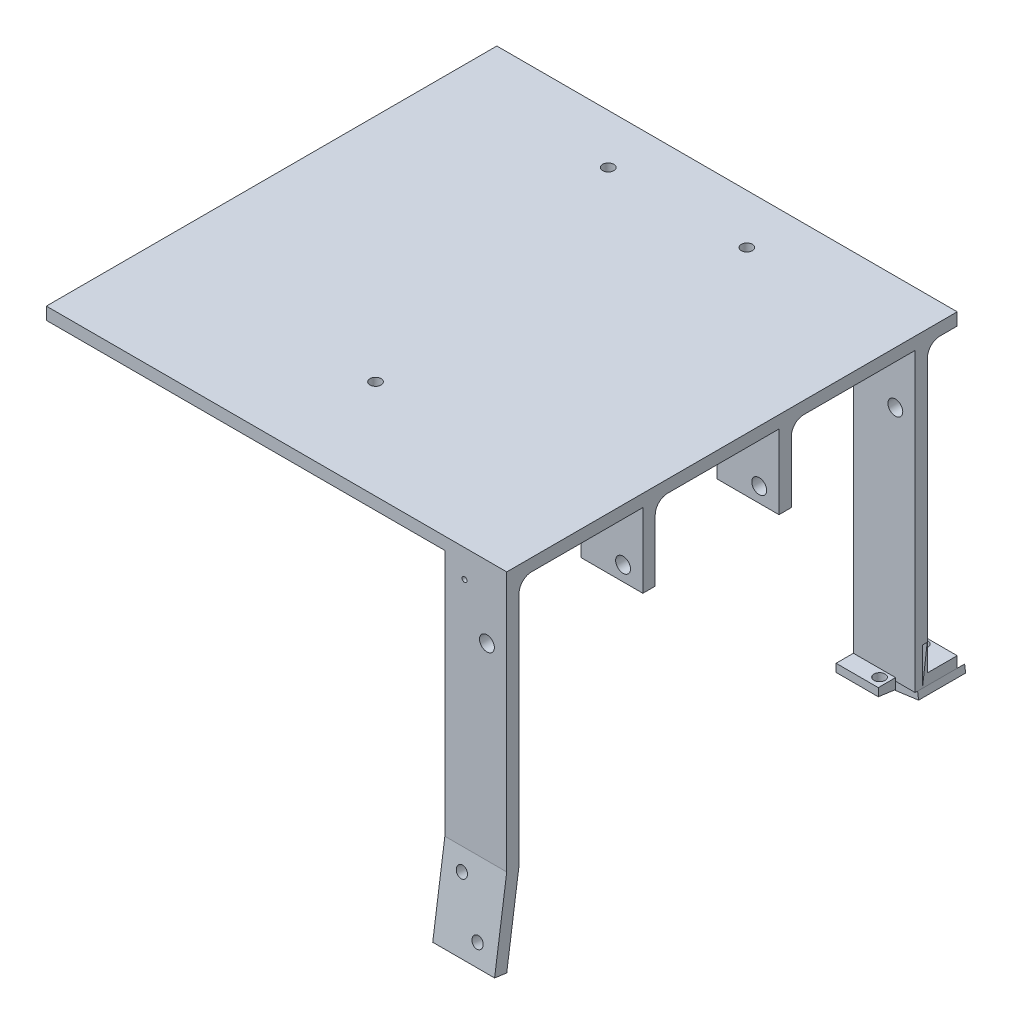
SolidWorks part; units mm, degrees
ref_plane "Front Plane" through (0, 0, 0) normal (0, 0, 1) x (1, 0, 0)
ref_plane "Top Plane" through (0, 0, 0) normal (0, 1, 0) x (1, 0, 0)
ref_plane "Right Plane" through (0, 0, 0) normal (1, 0, 0) x (0, 0, -1)
sketch "Sketch1" plane through (0, 0, 0) normal (0, 1, 0) x (1, 0, 0)
  line L0 (0, 0) -> (0, -300)
  line L1 (0, -300) -> (186, -300)
  line L2 (186, -300) -> (186, 0)
  line L3 (186, 0) -> (176, 0)
  line L4 (176, 0) -> (151, 0)
  line L5 (151, 0) -> (151, -56.1159)
  line L6 (151, -56.1159) -> (35, -56.1159)
  line L7 (35, -56.1159) -> (35, 0)
  line L8 (35, 0) -> (10, 0)
  line L9 (10, 0) -> (0, 0)
  line L10 (93, -300) -> (93, -56.1159) construction
  point P9 (93, -56.1159)
  dimension "D1" = 300
  dimension "D2" = 10
  dimension "D3" = 186
  dimension "D5" = 10
  dimension "D6" = 35
extrude "Boss-Extrude1" add sketch "Sketch1" along normal blind 5
sketch "Sketch2" plane through (0, 0, 0) normal (0, -1, 0) x (1, 0, 0)
  line L1 (50.5, 94) -> (55.5, 94)
  line L2 (50.5, 94) -> (50.5, 71.5)
  line L3 (50.5, 71.5) -> (55.5, 71.5)
  line L4 (55.5, 94) -> (55.5, 71.5)
  line L6 (135.5, 94) -> (130.5, 94)
  line L7 (135.5, 94) -> (135.5, 71.5)
  line L8 (135.5, 71.5) -> (130.5, 71.5)
  line L9 (130.5, 94) -> (130.5, 71.5)
  line L10 (0, 300) -> (186, 300) construction
  line L11 (186, 300) -> (186, 0) construction
  line L12 (0, 0) -> (0, 300) construction
  dimension "D1" = 5
  dimension "D2" = 22.5
  dimension "D3" = 5
  dimension "D4" = 206
  dimension "D5" = 22.5
  dimension "D6" = 50.5
  dimension "D7" = 50.5
extrude "Boss-Extrude2" add sketch "Sketch2" along normal blind 38
sketch "Sketch5" plane through (0, 0, 0) normal (0, -1, 0) x (1, 0, 0)
  line L0 (186, 300) -> (186, 0) construction
  line L1 (186, 295) -> (161, 295)
  line L2 (186, 295) -> (186, 300)
  line L3 (186, 300) -> (161, 300)
  line L4 (161, 295) -> (161, 300)
  line L5 (0, 300) -> (186, 300) construction
  line L6 (186, 240) -> (161, 240)
  line L7 (186, 240) -> (186, 245)
  line L8 (186, 245) -> (161, 245)
  line L9 (161, 240) -> (161, 245)
  line L10 (186, 185) -> (161, 185)
  line L11 (186, 185) -> (186, 190)
  line L12 (186, 190) -> (161, 190)
  line L13 (161, 185) -> (161, 190)
  line L14 (186, 130) -> (161, 130)
  line L15 (186, 130) -> (186, 135)
  line L16 (186, 135) -> (161, 135)
  line L17 (161, 130) -> (161, 135)
  dimension "D1" = 5
  dimension "D2" = 5
  dimension "D3" = 5
  dimension "D4" = 5
  dimension "D5" = 50
  dimension "D6" = 50
  dimension "D7" = 50
  dimension "D8" = 25
extrude "Boss-Extrude3" add sketch "Sketch5" along normal blind 30
fillet "Fillet3" radius 5 4 edges at (173.5, 0, 130) (173.5, 0, 185) (173.5, 0, 240) (173.5, 0, 295)
sketch "Sketch6" plane through (0, 0, 300) normal (0, 0, 1) x (1, 0, 0)
  line L0 (186, -30) -> (161, -30) construction
  line L1 (186, 5) -> (186, -30) construction
  circle A0 centre (178, -24) radius 3
  dimension "D1" = 6
  dimension "D2" = 6
  dimension "D3" = 8
extrude "Cut-Extrude4" cut sketch "Sketch6" against normal blind 172
sketch "Sketch7" plane through (0, 0, 0) normal (0, -1, 0) x (1, 0, 0)
  line L0 (0, 0) -> (0, 300) construction
  line L1 (0, 22.5) -> (5, 22.5)
  line L2 (0, 22.5) -> (0, 0)
  line L3 (0, 0) -> (5, 0)
  line L4 (5, 22.5) -> (5, 0)
  line L5 (186, 125) -> (186, 0) construction
  line L6 (186, 22.5) -> (181, 22.5)
  line L7 (186, 22.5) -> (186, 0)
  line L8 (186, 0) -> (181, 0)
  line L9 (181, 22.5) -> (181, 0)
  line L10 (186, 0) -> (151, 0) construction
  dimension "D1" = 5
  dimension "D2" = 5
  dimension "D3" = 22.5
  dimension "D4" = 22.5
extrude "Boss-Extrude4" add sketch "Sketch7" along normal blind 51.5
sketch "Sketch3" plane through (186, 0, 0) normal (1, 0, 0) x (0, 0, -1)
  line L4 (-71.5, 0) -> (-94, 0)
  line L5 (-71.5, -38) -> (-71.5, 0)
  line L6 (-94, -38) -> (-71.5, -38)
  line L7 (-94, 0) -> (-94, -38)
  line L9 (-71.5, -38) -> (-71.5, 0)
  line L10 (-94, -38) -> (-71.5, -38)
  line L11 (-94, 0) -> (-94, -38)
  line L13 (-71.5, 0) -> (-94, 0)
  circle A0 centre (-74, -32.9) radius 1.3 construction
  circle A1 centre (-91.5, -32.9) radius 1.3 construction
  circle A2 centre (-74, -32.9) radius 1.3
  circle A3 centre (-91.5, -32.9) radius 1.3
  circle A4 centre (-20, -46.4) radius 1.3 construction
  circle A5 centre (-2.5, -46.4) radius 1.3 construction
  circle A6 centre (-20, -46.4) radius 1.3
  circle A7 centre (-2.5, -46.4) radius 1.3
  dimension "D1" = 0
extrude "Cut-Extrude2" cut sketch "Sketch3" against normal through all contours A3 | A2 | A6 | A7
sketch "Sketch9" plane through (0, 0, 0) normal (0, -1, 0) x (1, 0, 0)
  line L0 (35, 0) -> (5, 0) construction
  line L1 (35, 0) -> (151, 0)
  line L2 (35, 0) -> (35, 63.7796)
  line L3 (35, 63.7796) -> (151, 63.7796)
  line L4 (151, 0) -> (151, 63.7796)
  line L5 (35, 56.1159) -> (35, 0) construction
  line L6 (151, 0) -> (151, 56.1159) construction
extrude "Cut-Extrude6" cut sketch "Sketch9" against normal blind 10
sketch "Sketch10" plane through (0, -30, 0) normal (0, -1, 0) x (1, 0, 0)
  line L1 (186, 295) -> (161, 295)
  line L2 (186, 295) -> (186, 300)
  line L3 (186, 300) -> (161, 300)
  line L4 (161, 295) -> (161, 300)
  line L5 (161, 130) -> (186, 130)
  line L6 (161, 130) -> (161, 135)
  line L7 (161, 135) -> (186, 135)
  line L8 (186, 130) -> (186, 135)
extrude "Boss-Extrude5" add sketch "Sketch10" along normal blind 70
sketch "Sketch11" plane through (186, 0, 0) normal (1, 0, 0) x (0, 0, -1)
  line L0 (-300, -100) -> (-304.9019, -134.6439)
  line L1 (-304.9019, -134.6439) -> (-300, -135.3374)
  line L2 (-300, -135.3374) -> (-295, -100)
  line L3 (-300, -100) -> (-295, -100)
extrude "Boss-Extrude6" add sketch "Sketch11" against normal blind 25
sketch "Sketch12" plane through (0, -100, 0) normal (0, -1, 0) x (1, 0, 0)
  line L1 (161, 130) -> (186, 130)
  line L2 (161, 130) -> (161, 135)
  line L3 (161, 135) -> (186, 135)
  line L4 (186, 130) -> (186, 135)
extrude "Boss-Extrude7" add sketch "Sketch12" along normal blind 19.72
sketch "Sketch13" plane through (0, 0, 130) normal (0, 0, -1) x (-1, 0, 0)
  line L0 (-186, -115.3141) -> (-186, -119.72)
  line L1 (-186, -119.72) -> (-186, -5) construction
  line L2 (-186, -119.72) -> (-161, -123.1352)
  line L3 (-161, -123.1352) -> (-161, -115.3141)
  line L4 (-161, -115.3141) -> (-186, -115.3141)
  line L5 (-161, -119.72) -> (-161, -5) construction
  line L8 (-88.5025, -135.5903) -> (-182.3051, -122.7762) construction
extrude "Boss-Extrude8" add sketch "Sketch13" along normal blind 15 and the other way blind 4
sketch "Sketch14" plane through (19.4625, -142.4702, 0) normal (0.1354, -0.9908, 0) x (0.9908, 0.1354, 0)
  line L0 (186.3576, 115) -> (168.0843, 132.0374)
  line L1 (168.0843, 115) -> (142.8521, 115) construction
  line L2 (168.0843, 115) -> (168.0843, 134) construction
  line L3 (168.0843, 132.0374) -> (198.0152, 130.431)
  line L4 (198.0152, 130.431) -> (197.5151, 111.3666)
  line L5 (197.5151, 111.3666) -> (186.3576, 109.6075)
  line L6 (186.3576, 109.6075) -> (186.3576, 115)
extrude "Cut-Extrude7" cut sketch "Sketch14" against normal blind 15
sketch "Sketch15" plane through (0, 39.652, 280.2402) normal (0, 0.1401, 0.9901) x (1, 0, 0)
  line L1 (161, -141.043) -> (161, -176.032) construction
  line L2 (186, -141.043) -> (161, -141.043) construction
  line L3 (186, -141.043) -> (186, -176.032) construction
  line L4 (161, -176.032) -> (186, -176.032) construction
  circle A0 centre (178, -168.032) radius 2.25
  circle A1 centre (169, -149.043) radius 2.25
  dimension "D1" = 4.5
  dimension "D2" = 4.5
  dimension "D3" = 8
  dimension "D4" = 8
  dimension "D5" = 8
  dimension "D6" = 8
extrude "Cut-Extrude8" cut sketch "Sketch15" against normal blind 20
sketch "Sketch16" plane through (0, 0, 0) normal (0, -1, 0) x (1, 0, 0)
  line L1 (166, 272) -> (172, 272)
  line L2 (166, 272) -> (166, 275)
  line L3 (166, 275) -> (172, 275)
  line L4 (172, 272) -> (172, 275)
  line L5 (143.4, 272) -> (137.4, 272)
  line L6 (143.4, 272) -> (143.4, 275)
  line L7 (143.4, 275) -> (137.4, 275)
  line L8 (137.4, 272) -> (137.4, 275)
  line L9 (166, 217) -> (172, 217)
  line L10 (166, 217) -> (166, 220)
  line L11 (166, 220) -> (172, 220)
  line L12 (172, 217) -> (172, 220)
  line L13 (166, 162) -> (172, 162)
  line L14 (166, 162) -> (166, 165)
  line L15 (166, 165) -> (172, 165)
  line L16 (172, 162) -> (172, 165)
  line L17 (137.4, 217) -> (143.4, 217)
  line L18 (137.4, 217) -> (137.4, 220)
  line L19 (137.4, 220) -> (143.4, 220)
  line L20 (143.4, 217) -> (143.4, 220)
  line L21 (137.4, 162) -> (143.4, 162)
  line L22 (137.4, 162) -> (137.4, 165)
  line L23 (137.4, 165) -> (143.4, 165)
  line L24 (143.4, 162) -> (143.4, 165)
  line L25 (186, 180) -> (186, 135) construction
  line L28 (161, 295) -> (186, 295) construction
  line L29 (161, 240) -> (186, 240) construction
  line L30 (161, 185) -> (186, 185) construction
  dimension "D1" = 3
  dimension "D2" = 3
  dimension "D3" = 3
  dimension "D4" = 3
  dimension "D5" = 3
  dimension "D6" = 3
  dimension "D7" = 20
  dimension "D8" = 22.6
  dimension "D9" = 6
  dimension "D10" = 6
  dimension "D11" = 23
  dimension "D12" = 23
  dimension "D13" = 23
extrude "Boss-Extrude9" add sketch "Sketch16" along normal blind 12.4
sketch "Sketch17" plane through (0, 0, 162) normal (0, 0, -1) x (-1, 0, 0)
  arc A0 (-169.75, -6.8) -> (-169.75, -5.6) centre (-168.95, -6.2) ccw construction
  arc A1 (-169.75, -6.8) -> (-169.75, -5.6) centre (-168.95, -6.2) ccw
  circle A2 centre (-168.95, -6.2) radius 1
  circle A3 centre (-140.45, -6.2) radius 1
extrude "Cut-Extrude9" cut sketch "Sketch17" against normal through all contours A1 A2 | A3 region at (168.95, -6.2, 162)
sketch "Sketch27" plane through (19.4625, -142.4702, 0) normal (0.1354, -0.9908, 0) x (0.9908, 0.1354, 0)
  line L1 (142.8521, 115) -> (168.0843, 115)
  line L2 (142.8521, 115) -> (142.8521, 134)
  line L3 (142.8521, 134) -> (168.0843, 134)
  line L4 (168.0843, 115) -> (168.0843, 134)
extrude "Boss-Extrude11" add sketch "Sketch27" along normal blind 3
fillet "Fillet4" radius 5 6 edges at (140.4, 0, 275) (169, 0, 275) (140.4, 0, 220) (169, 0, 220) (140.4, 0, 165) (169, 0, 165)
sketch "Sketch18" plane through (0, -115.3141, 0) normal (0, 1, 0) x (1, 0, 0)
  circle A0 centre (174.8857, -120.9947) radius 2.25
  dimension "D1" = 4.5
extrude "Cut-Extrude10" cut sketch "Sketch18" against normal through all
sketch "Sketch19" plane through (0, 0, 0) normal (0, -1, 0) x (1, 0, 0)
  line L0 (42.3, 80.75) -> (39.8, 80.75) construction
  line L1 (39.8, 84.75) -> (39.8, 80.75) construction
  line L2 (42.3, 84.75) -> (42.3, 80.75) construction
  line L3 (39.8, 84.75) -> (42.3, 84.75) construction
  line L4 (42.3, 80.75) -> (39.8, 80.75) construction
  line L5 (39.8, 84.75) -> (39.8, 80.75) construction
  line L6 (42.3, 84.75) -> (42.3, 80.75) construction
  line L7 (39.8, 84.75) -> (42.3, 84.75) construction
  line L8 (143.7, 80.75) -> (143.7, 84.75) construction
  line L9 (143.7, 84.75) -> (146.2, 84.75) construction
  line L10 (146.2, 80.75) -> (146.2, 84.75) construction
  line L11 (146.2, 80.75) -> (143.7, 80.75) construction
  line L12 (143.7, 80.75) -> (143.7, 84.75) construction
  line L13 (143.7, 84.75) -> (146.2, 84.75) construction
  line L14 (146.2, 80.75) -> (146.2, 84.75) construction
  line L15 (146.2, 80.75) -> (143.7, 80.75) construction
  line L16 (43.3, 79.75) -> (38.8, 79.75)
  line L17 (38.8, 85.75) -> (38.8, 79.75)
  line L18 (38.8, 85.75) -> (43.3, 85.75)
  line L19 (43.3, 85.75) -> (43.3, 79.75)
  line L20 (142.7, 79.75) -> (142.7, 85.75)
  line L21 (142.7, 85.75) -> (147.2, 85.75)
  line L22 (147.2, 79.75) -> (147.2, 85.75)
  line L23 (147.2, 79.75) -> (142.7, 79.75)
  line L31 (151, 0) -> (181, 0)
  line L32 (181, 0) -> (181, 22.5)
  line L34 (186, 22.5) -> (186, 125)
  line L35 (186, 125) -> (161, 125)
  line L36 (161, 125) -> (161, 135)
  line L37 (161, 135) -> (186, 135)
  line L38 (186, 135) -> (186, 180)
  line L39 (186, 180) -> (161, 180)
  line L40 (161, 180) -> (161, 190)
  line L41 (161, 190) -> (186, 190)
  line L42 (186, 190) -> (186, 235)
  line L43 (186, 235) -> (161, 235)
  line L44 (161, 235) -> (161, 245)
  line L45 (161, 245) -> (186, 245)
  line L46 (186, 245) -> (186, 290)
  line L47 (186, 290) -> (161, 290)
  line L48 (161, 290) -> (161, 300)
  line L49 (161, 300) -> (0, 300)
  line L50 (0, 300) -> (0, 22.5)
  line L51 (0, 22.5) -> (5, 22.5)
  line L52 (5, 22.5) -> (5, 0)
  line L53 (5, 0) -> (35, 0)
  line L56 (151, 63.7796) -> (151, 0)
  line L57 (151, 63.7796) -> (151, 0)
  line L58 (35, 0) -> (35, 63.7796)
  line L61 (151, 0) -> (181, 0)
  line L64 (186, 22.5) -> (186, 125)
  line L65 (186, 125) -> (161, 125)
  line L66 (161, 125) -> (161, 135)
  line L67 (161, 135) -> (186, 135)
  line L68 (186, 135) -> (186, 180)
  line L69 (186, 180) -> (161, 180)
  line L70 (161, 180) -> (161, 190)
  line L71 (161, 190) -> (186, 190)
  line L72 (186, 190) -> (186, 235)
  line L73 (186, 235) -> (161, 235)
  line L74 (161, 235) -> (161, 245)
  line L75 (161, 245) -> (186, 245)
  line L76 (186, 245) -> (186, 290)
  line L77 (186, 290) -> (161, 290)
  line L78 (161, 290) -> (161, 300)
  line L79 (161, 300) -> (0, 300)
  line L80 (0, 300) -> (0, 22.5)
  line L81 (0, 22.5) -> (5, 22.5)
  line L82 (5, 22.5) -> (5, 0)
  line L83 (5, 0) -> (35, 0)
  line L106 (35, 0) -> (35, 63.7796)
  line L107 (35, 63.7796) -> (151, 63.7796)
  line L108 (35, 63.7796) -> (151, 63.7796)
  line L116 (181, 22.5) -> (186, 22.5)
  line L122 (181, 22.5) -> (186, 22.5)
  line L124 (181, 0) -> (181, 22.5)
  dimension "D1" = 0
  dimension "D2" = 1
  dimension "D3" = 1
extrude "Cut-Extrude12" cut sketch "Sketch19" against normal through all contours L23 L22 L21 L20 | L19 L18 L17 L16 region at (41.05, 0, 82.75) region at (144.95, 0, 82.75)
fillet "Fillet6" radius 10 2 edges at (151, 2.5, 63.7796) (35, 2.5, 63.7796)
sketch "Sketch21" plane through (0, 0, 0) normal (0, -1, 0) x (1, 0, 0)
  line L0 (0, 22.5) -> (0, 300) construction
  line L1 (0, 48) -> (27, 48)
  line L2 (0, 48) -> (0, 118)
  line L3 (0, 118) -> (27, 118)
  line L4 (27, 48) -> (27, 118)
  line L5 (186, 125) -> (186, 22.5) construction
  line L6 (186, 48) -> (159, 48)
  line L7 (186, 48) -> (186, 118)
  line L8 (186, 118) -> (159, 118)
  line L9 (159, 48) -> (159, 118)
  line L10 (0, 300) -> (161, 300) construction
  dimension "D1" = 70
  dimension "D2" = 182
  dimension "D3" = 70
  dimension "D4" = 182
  dimension "D5" = 27
  dimension "D6" = 27
extrude "Cut-Extrude14" cut sketch "Sketch21" against normal through all
fillet "Fillet7" radius 10 4 edges at (27, 2.5, 118) (27, 2.5, 48) (159, 2.5, 48) (159, 2.5, 118)
fillet "Fillet8" radius 2.5 2 edges at (55.5, 0, 82.75) (130.5, 0, 82.75)
sketch "Sketch22" plane through (0, 0, 0) normal (0, -1, 0) x (1, 0, 0)
  line L34 (17, 48) -> (0, 48)
  line L35 (0, 48) -> (0, 22.5)
  line L36 (0, 22.5) -> (5, 22.5)
  line L37 (5, 22.5) -> (5, 0)
  line L38 (5, 0) -> (35, 0)
  line L39 (35, 0) -> (35, 53.7796)
  line L40 (45, 63.7796) -> (141, 63.7796)
  line L41 (151, 53.7796) -> (151, 0)
  line L42 (151, 0) -> (181, 0)
  line L43 (181, 0) -> (181, 22.5)
  line L44 (181, 22.5) -> (186, 22.5)
  line L45 (186, 22.5) -> (186, 48)
  line L46 (186, 48) -> (169, 48)
  line L47 (159, 58) -> (159, 108)
  line L48 (169, 118) -> (186, 118)
  line L49 (186, 118) -> (186, 125)
  line L50 (186, 125) -> (161, 125)
  line L51 (161, 125) -> (161, 135)
  line L52 (161, 135) -> (186, 135)
  line L53 (186, 135) -> (186, 180)
  line L54 (186, 180) -> (161, 180)
  line L55 (161, 180) -> (161, 190)
  line L56 (161, 190) -> (186, 190)
  line L57 (186, 190) -> (186, 235)
  line L58 (186, 235) -> (161, 235)
  line L59 (161, 235) -> (161, 245)
  line L60 (161, 245) -> (186, 245)
  line L61 (186, 245) -> (186, 290)
  line L62 (186, 290) -> (161, 290)
  line L63 (161, 290) -> (161, 300)
  line L64 (161, 300) -> (0, 300)
  line L65 (0, 300) -> (0, 118)
  line L66 (0, 118) -> (17, 118)
  line L67 (27, 108) -> (27, 58)
  line L68 (17, 48) -> (0, 48)
  line L69 (0, 48) -> (0, 22.5)
  line L70 (0, 22.5) -> (5, 22.5)
  line L71 (5, 22.5) -> (5, 0)
  line L72 (5, 0) -> (35, 0)
  line L73 (35, 0) -> (35, 53.7796)
  line L74 (45, 63.7796) -> (141, 63.7796)
  line L75 (151, 53.7796) -> (151, 0)
  line L76 (151, 0) -> (181, 0)
  line L77 (181, 0) -> (181, 22.5)
  line L78 (181, 22.5) -> (186, 22.5)
  line L79 (186, 22.5) -> (186, 48)
  line L80 (186, 48) -> (169, 48)
  line L81 (159, 58) -> (159, 108)
  line L82 (169, 118) -> (186, 118)
  line L83 (186, 118) -> (186, 125)
  line L84 (186, 125) -> (161, 125)
  line L85 (161, 125) -> (161, 135)
  line L86 (161, 135) -> (186, 135)
  line L87 (186, 135) -> (186, 180)
  line L88 (186, 180) -> (161, 180)
  line L89 (161, 180) -> (161, 190)
  line L90 (161, 190) -> (186, 190)
  line L91 (186, 190) -> (186, 235)
  line L92 (186, 235) -> (161, 235)
  line L93 (161, 235) -> (161, 245)
  line L94 (161, 245) -> (186, 245)
  line L95 (186, 245) -> (186, 290)
  line L96 (186, 290) -> (161, 290)
  line L97 (161, 290) -> (161, 300)
  line L98 (161, 300) -> (0, 300)
  line L99 (0, 300) -> (0, 118)
  line L100 (0, 118) -> (17, 118)
  line L101 (27, 108) -> (27, 58)
  circle A0 centre (115, 72.25) radius 2.25 construction
  circle A1 centre (115, 72.25) radius 2.25
  circle A2 centre (71, 72.25) radius 2.25 construction
  circle A3 centre (71, 72.25) radius 2.25
  circle A4 centre (24.5, 25.25) radius 2.25 construction
  circle A5 centre (24.5, 25.25) radius 2.25
  arc A6 (45, 63.7796) -> (35, 53.7796) centre (45, 53.7796) ccw
  arc A7 (151, 53.7796) -> (141, 63.7796) centre (141, 53.7796) ccw
  arc A8 (159, 58) -> (169, 48) centre (169, 58) ccw
  arc A9 (169, 118) -> (159, 108) centre (169, 108) ccw
  arc A10 (27, 108) -> (17, 118) centre (17, 108) ccw
  arc A11 (17, 48) -> (27, 58) centre (17, 58) ccw
  arc A12 (45, 63.7796) -> (35, 53.7796) centre (45, 53.7796) ccw
  arc A13 (151, 53.7796) -> (141, 63.7796) centre (141, 53.7796) ccw
  arc A14 (159, 58) -> (169, 48) centre (169, 58) ccw
  arc A15 (169, 118) -> (159, 108) centre (169, 108) ccw
  arc A16 (27, 108) -> (17, 118) centre (17, 108) ccw
  arc A17 (17, 48) -> (27, 58) centre (17, 58) ccw
  circle A18 centre (161.5, 25.6175) radius 2.25 construction
  circle A19 centre (161.5, 25.6175) radius 2.25
  dimension "D1" = 0
extrude "Cut-Extrude16" cut sketch "Sketch22" against normal blind 10 contours A5 | A3 | A1 | A19
sketch "Sketch23" plane through (0, 0, 135) normal (0, 0, 1) x (1, 0, 0)
  line L1 (178.1063, -118.4368) -> (161.0628, -118.4368)
  line L2 (178.1063, -118.4368) -> (178.1063, -123.5756)
  line L3 (178.1063, -123.5756) -> (161.0628, -123.5756)
  line L4 (161.0628, -118.4368) -> (161.0628, -123.5756)
extrude "Boss-Extrude10" add sketch "Sketch23" along normal blind 7
sketch "Sketch24" plane through (161.0628, 0, 0) normal (-1, 0, 0) x (0, 0, 1)
  line L0 (295, -100) -> (133.6076, -122.8359) construction
  line L1 (142, -121.6484) -> (135, -122.6389)
  line L2 (135, -119.72) -> (135, -123.5756) construction
  line L3 (142, -118.4368) -> (142, -123.5756) construction
  line L4 (142, -121.6484) -> (142, -124.3381)
  line L5 (142, -124.3381) -> (134.715, -124.3381)
  line L6 (134.715, -124.3381) -> (135, -122.6389)
extrude "Cut-Extrude17" cut sketch "Sketch24" against normal up to next
sketch "Sketch25" plane through (0, -118.4368, 0) normal (0, 1, 0) x (1, 0, 0)
  circle A0 centre (174.7191, -138.0894) radius 2.25
  dimension "D1" = 4.5
extrude "Cut-Extrude18" cut sketch "Sketch25" against normal up to next
sketch "Sketch28" plane through (0, 5, 0) normal (0, 1, 0) x (1, 0, 0)
  line L0 (0, -300) -> (186, -300) construction
  circle A0 centre (93, -260) radius 2.25
  point P4 (93, -300)
  dimension "D1" = 4.5
  dimension "D2" = 40
extrude "Cut-Extrude19" cut sketch "Sketch28" against normal through all
sketch "Sketch29" plane through (0, 0, 0) normal (0, -1, 0) x (1, 0, 0)
  line L1 (0, 0) -> (186, 0)
  line L2 (0, 0) -> (0, 118)
  line L3 (0, 118) -> (186, 118)
  line L4 (186, 0) -> (186, 118)
extrude "Cut-Extrude20" cut sketch "Sketch29" against normal blind 10 and the other way blind 126
sketch "Sketch30" plane through (0, 0, 0) normal (0, -1, 0) x (1, 0, 0)
  line L0 (0, 118) -> (0, 300) construction
  line L1 (186, 118) -> (0, 118) construction
  line L2 (186, 180) -> (186, 135) construction
  circle A0 centre (65, 138) radius 2.25
  circle A1 centre (121, 138) radius 2.25
  dimension "D1" = 4.5
  dimension "D2" = 4.5
  dimension "D3" = 65
  dimension "D4" = 20
  dimension "D5" = 20
  dimension "D6" = 65
extrude "Cut-Extrude21" cut sketch "Sketch30" against normal through all
